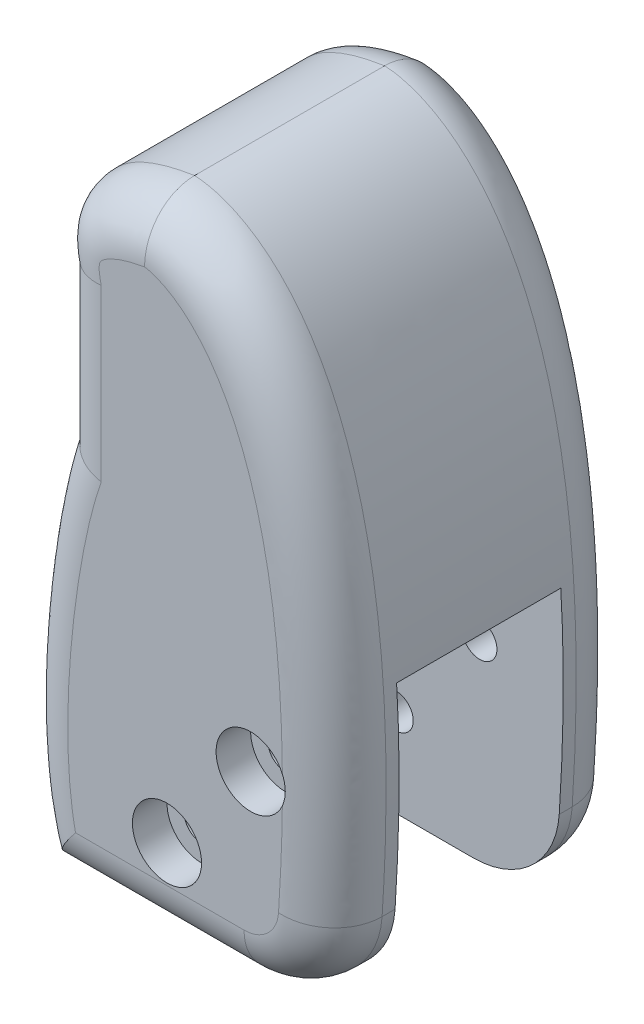
SolidWorks part; units mm, degrees
ref_plane "Спереди" through (0, 0, 0) normal (0, 0, 1) x (1, 0, 0)
ref_plane "Сверху" through (0, 0, 0) normal (0, 1, 0) x (1, 0, 0)
ref_plane "Справа" through (0, 0, 0) normal (1, 0, 0) x (0, 0, -1)
sketch "Sketch1" plane through (0, 0, 0) normal (0, 0, 1) x (1, 0, 0)
  line L0 (6.0546, 33.7859) -> (-0.2781, 32.8291) construction
  line L1 (9.4074, 33.6617) -> (19.7802, 29.1537) construction
  line L2 (19.7802, 29.1537) -> (16.5087, -2.5955) construction
  line L3 (16.5087, -2.5955) -> (0, -2.5955)
  line L4 (6.0546, 33.7859) -> (9.4074, 33.6617) construction
  line L5 (0.6531, 19.2164) -> (-1.0738, 13.971) construction
  line L6 (-1.0738, 13.971) -> (-2.3436, 2.3786) construction
  line L7 (-2.3436, 2.3786) -> (0, -2.5955) construction
  line L8 (-0.2781, 32.8291) -> (0.6531, 28.2762) construction
  line L9 (0.6531, 28.2762) -> (0.6531, 19.2164)
  circle A0 centre (7.458, 2.5388) radius 1
  spline S0 degree 3 poles (6.0546, 33.7859) (9.4074, 33.6617) (19.7802, 29.1537) (16.5087, -2.5955) knots 0 0 0 0 1 1 1 1
  spline S1 degree 3 poles (0.6531, 19.2164) (-1.0738, 13.971) (-2.3436, 2.3786) (0, -2.5955) knots 0 0 0 0 1 1 1 1
  spline S2 degree 2 poles (6.0546, 33.7859) (-0.2781, 32.8291) (0.6531, 28.2762) knots 0 0 0 1 1 1
  dimension "D1" = 2
extrude "Boss-Extrude1" add sketch "Sketch1" along normal mid plane 17
sketch "Sketch2" plane through (0, 0, 0) normal (0, 0, 1) x (1, 0, 0)
  line L0 (-2.7344, 4.9245) -> (11.1609, 18.3696) construction
  line L1 (11.1609, 18.3696) -> (19.7322, 11.9598) construction
  line L2 (-2.7344, 4.9245) -> (-2.7344, -3.1505)
  line L3 (-2.7344, -3.1505) -> (19.7322, -3.1505)
  line L4 (19.7322, 11.9598) -> (19.7322, -3.1505)
  spline S0 degree 2 poles (-2.7344, 4.9245) (11.1609, 18.3696) (19.7322, 11.9598) knots 0 0 0 1 1 1
extrude "Cut-Extrude1" cut sketch "Sketch2" against normal mid plane 9.5
sketch "Sketch3" plane through (0, 0, 0) normal (0, 0, 1) x (1, 0, 0)
  circle A0 centre (12.2997, 8.5381) radius 1
  dimension "D1" = 2
extrude "Cut-Extrude2" cut sketch "Sketch3" against normal blind 27 and the other way blind 27
fillet "Fillet2" radius 5 2 edges at (16.5087, -2.5955, 6.625) (16.5087, -2.5955, -6.625)
fillet "Fillet3" radius 3 12 edges at (5.9589, -2.5955, 8.5) (15.3342, -1.2463, 8.5) (5.9589, -2.5955, -8.5) (15.3342, -1.2463, -8.5) (0.6531, 23.7463, 8.5) (0.6531, 23.7463, -8.5)
sketch "Sketch4" plane through (0, 0, 8.5) normal (0, 0, 1) x (1, 0, 0)
  circle A0 centre (12.2997, 8.5381) radius 2
  circle A1 centre (7.458, 2.5388) radius 2
  dimension "D1" = 4
extrude "Cut-Extrude3" cut sketch "Sketch4" against normal blind 2
sketch "Sketch6" plane through (0, 0, -8.5) normal (0, 0, -1) x (-1, 0, 0)
  line L0 (-12.623, 6.1932) -> (-10.4306, 7.0857)
  line L1 (-10.4306, 7.0857) -> (-10.1073, 9.4306)
  line L2 (-10.1073, 9.4306) -> (-11.9764, 10.8831)
  line L3 (-11.9764, 10.8831) -> (-14.1689, 9.9906)
  line L4 (-14.1689, 9.9906) -> (-14.4922, 7.6457)
  line L5 (-14.4922, 7.6457) -> (-12.623, 6.1932)
  line L6 (-11.9764, 10.8831) -> (-12.623, 6.1932) construction
  line L7 (-10.4306, 7.0857) -> (-14.1689, 9.9906) construction
  line L8 (-7.7813, 0.1938) -> (-5.5889, 1.0863)
  line L9 (-5.5889, 1.0863) -> (-5.2656, 3.4313)
  line L10 (-5.2656, 3.4313) -> (-7.1347, 4.8837)
  line L11 (-7.1347, 4.8837) -> (-9.3271, 3.9912)
  line L12 (-9.3271, 3.9912) -> (-9.6504, 1.6463)
  line L13 (-9.6504, 1.6463) -> (-7.7813, 0.1938)
  line L14 (-7.1347, 4.8837) -> (-7.7813, 0.1938) construction
  line L15 (-5.5889, 1.0863) -> (-9.3271, 3.9912) construction
  point P6 (-12.2997, 8.5381)
  point P7 (-12.2997, 8.5381)
  point P8 (-7.458, 2.5388)
  point P15 (-7.458, 2.5388)
extrude "Cut-Extrude5" cut sketch "Sketch6" against normal blind 2
